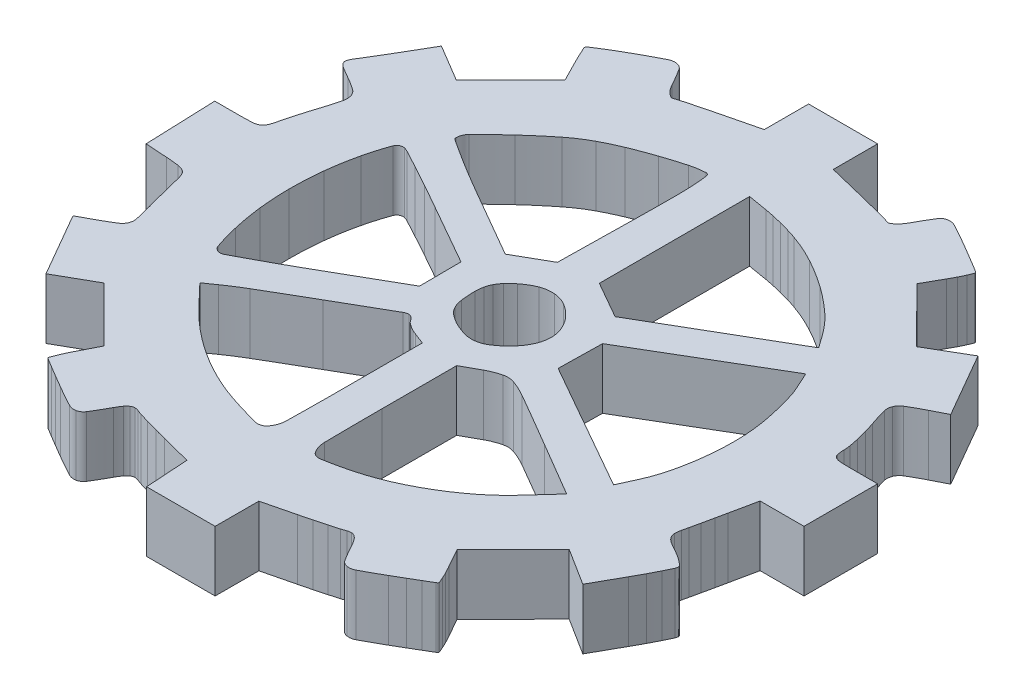
SolidWorks part; units mm, degrees
ref_plane "Front Plane" through (0, 0, 0) normal (0, 0, 1) x (1, 0, 0)
ref_plane "Top Plane" through (0, 0, 0) normal (0, 1, 0) x (1, 0, 0)
ref_plane "Right Plane" through (0, 0, 0) normal (1, 0, 0) x (0, 0, -1)
sketch "Sketch1" plane through (0, 0, 0) normal (0, 1, 0) x (1, 0, 0)
  line L30 (6921.7474, 9184.2888) -> (6921.7474, 9183.9218)
  line L31 (6921.7474, 9183.9218) -> (6921.195, 9183.7863)
  line L32 (6919.2339, 9183.2823) -> (6919.3873, 9182.9815)
  line L33 (6919.3873, 9182.9815) -> (6918.9372, 9182.5315)
  line L34 (6918.9372, 9182.5315) -> (6918.4872, 9182.0815)
  line L35 (6918.4872, 9182.0815) -> (6918.1815, 9182.2638)
  line L36 (6918.1815, 9182.2638) -> (6917.8757, 9182.4461)
  line L37 (6917.8757, 9182.4461) -> (6917.6654, 9182.0841)
  line L38 (6917.1708, 9179.7791) -> (6916.788, 9179.7791)
  line L39 (6916.788, 9179.7791) -> (6916.8103, 9179.1885)
  line L40 (6916.8103, 9179.1885) -> (6916.8325, 9178.598)
  line L41 (6916.8325, 9178.598) -> (6917.1941, 9178.5748)
  line L42 (6917.465, 9177.0712) -> (6917.2593, 9176.9598)
  line L43 (6917.2593, 9176.9598) -> (6917.5633, 9176.4325)
  line L44 (6917.5633, 9176.4325) -> (6917.8673, 9175.9052)
  line L45 (6917.8673, 9175.9052) -> (6918.1735, 9176.0791)
  line L46 (6918.1735, 9176.0791) -> (6918.4796, 9176.253)
  line L47 (6918.4796, 9176.253) -> (6918.9314, 9175.8012)
  line L48 (6918.9314, 9175.8012) -> (6919.3832, 9175.3494)
  line L49 (6919.3832, 9175.3494) -> (6919.2265, 9175.0423)
  line L50 (6921.214, 9174.5238) -> (6921.7093, 9174.3973)
  line L51 (6921.7093, 9174.3973) -> (6921.7326, 9174.0402)
  line L52 (6921.7326, 9174.0402) -> (6921.7558, 9173.6831)
  line L53 (6921.7558, 9173.6831) -> (6922.3231, 9173.6831)
  line L54 (6922.3231, 9173.6831) -> (6922.8904, 9173.6831)
  line L55 (6922.8904, 9173.6831) -> (6922.891, 9174.045)
  line L56 (6922.891, 9174.045) -> (6922.8915, 9174.407)
  line L57 (6922.8915, 9174.407) -> (6923.4053, 9174.533)
  line L58 (6925.3838, 9174.6199) -> (6925.5248, 9174.7034)
  line L59 (6925.4013, 9175.0451) -> (6925.2297, 9175.3504)
  line L60 (6925.2297, 9175.3504) -> (6925.692, 9175.8171)
  line L61 (6925.692, 9175.8171) -> (6926.1544, 9176.2838)
  line L62 (6926.1544, 9176.2838) -> (6926.4603, 9176.0907)
  line L63 (6926.4603, 9176.0907) -> (6926.7662, 9175.8976)
  line L64 (6926.7662, 9175.8976) -> (6927.0381, 9176.3839)
  line L65 (6926.9482, 9178.1217) -> (6927.0401, 9178.5599)
  line L66 (6927.0401, 9178.5599) -> (6927.4037, 9178.5599)
  line L67 (6927.4037, 9178.5599) -> (6927.7672, 9178.5599)
  line L68 (6927.7672, 9178.5599) -> (6927.7672, 9179.1695)
  line L69 (6927.7672, 9179.1695) -> (6927.7672, 9179.7791)
  line L70 (6927.7672, 9179.7791) -> (6927.3862, 9179.7791)
  line L71 (6927.1347, 9181.2554) -> (6927.3786, 9181.3792)
  line L72 (6927.3786, 9181.3792) -> (6927.0713, 9181.9122)
  line L73 (6927.0713, 9181.9122) -> (6926.764, 9182.4451)
  line L74 (6926.764, 9182.4451) -> (6926.4425, 9182.2567)
  line L75 (6926.4425, 9182.2567) -> (6926.121, 9182.0683)
  line L76 (6926.121, 9182.0683) -> (6925.6718, 9182.5222)
  line L77 (6925.6718, 9182.5222) -> (6925.2227, 9182.9761)
  line L78 (6925.2227, 9182.9761) -> (6925.3977, 9183.2876)
  line L79 (6923.4429, 9183.7863) -> (6922.8904, 9183.9218)
  line L80 (6922.8904, 9183.9218) -> (6922.8904, 9184.2888)
  line L81 (6922.8904, 9184.2888) -> (6922.8904, 9184.6559)
  line L82 (6922.8904, 9184.6559) -> (6922.3189, 9184.6559)
  line L83 (6922.3189, 9184.6559) -> (6921.7474, 9184.6559)
  line L84 (6921.7474, 9184.6559) -> (6921.7474, 9184.2888)
  line L85 (6921.9588, 9181.5656) -> (6921.9379, 9180.3042)
  line L86 (6921.9379, 9180.3042) -> (6921.6633, 9180.1473)
  line L87 (6921.6633, 9180.1473) -> (6921.3887, 9179.9905)
  line L88 (6921.3887, 9179.9905) -> (6920.3503, 9180.5896)
  line L89 (6925.1773, 9181.4542) -> (6925.3283, 9181.2422)
  line L90 (6925.3283, 9181.2422) -> (6924.2619, 9180.6226)
  line L91 (6924.2619, 9180.6226) -> (6923.1955, 9180.003)
  line L92 (6923.1955, 9180.003) -> (6922.8912, 9180.1768)
  line L93 (6922.8912, 9180.1768) -> (6922.5868, 9180.3506)
  line L94 (6922.5868, 9180.3506) -> (6922.5862, 9181.5955)
  line L95 (6922.5862, 9181.5955) -> (6922.5856, 9182.8405)
  line L96 (6922.5856, 9182.8405) -> (6922.9085, 9182.7859)
  line L97 (6925.7249, 9177.8626) -> (6925.5955, 9177.5778)
  line L98 (6925.5955, 9177.5778) -> (6924.5306, 9178.1835)
  line L99 (6924.5306, 9178.1835) -> (6923.4656, 9178.7892)
  line L100 (6923.4656, 9178.7892) -> (6923.4721, 9179.1508)
  line L101 (6923.4721, 9179.1508) -> (6923.4785, 9179.5124)
  line L102 (6923.4785, 9179.5124) -> (6924.537, 9180.1365)
  line L103 (6924.537, 9180.1365) -> (6925.5955, 9180.7606)
  line L104 (6925.5955, 9180.7606) -> (6925.7249, 9180.4761)
  line L105 (6920.1298, 9180.0839) -> (6921.1334, 9179.5124)
  line L106 (6921.1334, 9179.5124) -> (6921.1356, 9179.1667)
  line L107 (6921.1356, 9179.1667) -> (6921.1378, 9178.821)
  line L108 (6921.1378, 9178.821) -> (6920.1108, 9178.2333)
  line L109 (6921.7929, 9178.0999) -> (6921.976, 9178.0303)
  line L110 (6921.976, 9178.0303) -> (6921.976, 9176.7711)
  line L111 (6919.6138, 9176.691) -> (6919.2709, 9177.05)
  line L112 (6919.2709, 9177.05) -> (6919.452, 9177.1763)
  line L113 (6924.4381, 9177.5879) -> (6925.338, 9177.0582)
  line L114 (6925.338, 9177.0582) -> (6924.9564, 9176.6407)
  line L115 (6922.5858, 9176.7501) -> (6922.5861, 9177.9884)
  line L116 (6922.5861, 9177.9884) -> (6922.8716, 9178.1465)
  arc A414 (6921.195, 9183.7863) -> (6920.9768, 9183.7318) centre (6927.4959, 9158.0872) ccw
  arc A415 (6920.9768, 9183.7318) -> (6920.7782, 9183.6802) centre (6925.4996, 9165.9402) ccw
  arc A416 (6920.7782, 9183.6802) -> (6920.6122, 9183.6353) centre (6926.2112, 9163.2663) ccw
  arc A417 (6920.6122, 9183.6353) -> (6920.5518, 9183.6151) centre (6920.7702, 9183.0603) ccw
  arc A418 (6920.5087, 9183.6167) -> (6920.5518, 9183.6151) centre (6920.532, 9183.6652) ccw
  arc A419 (6920.4536, 9183.6529) -> (6920.5087, 9183.6167) centre (6920.6174, 9183.8424) ccw
  arc A420 (6920.3961, 9183.7143) -> (6920.4536, 9183.6529) centre (6920.7139, 9183.9542) ccw
  arc A421 (6920.345, 9183.7938) -> (6920.3961, 9183.7143) centre (6920.8975, 9184.0926) ccw
  arc A422 (6920.345, 9183.7938) -> (6920.1788, 9184.0777) centre (6916.0619, 9181.4769) ccw
  arc A423 (6920.1788, 9184.0777) -> (6920.0775, 9184.1463) centre (6920.0498, 9183.9962) ccw
  arc A424 (6920.0775, 9184.1463) -> (6919.9461, 9184.1272) centre (6920.0399, 9183.9429) ccw
  arc A425 (6919.9461, 9184.1272) -> (6919.5848, 9183.9343) centre (6924.7426, 9174.7113) ccw
  arc A426 (6919.5848, 9183.9343) -> (6919.3915, 9183.8236) centre (6925.1484, 9173.9858) ccw
  arc A427 (6919.3915, 9183.8236) -> (6919.2286, 9183.7249) centre (6922.4798, 9178.5461) ccw
  arc A428 (6919.2286, 9183.7249) -> (6919.0914, 9183.6377) centre (6927.0862, 9171.2084) ccw
  arc A429 (6919.0914, 9183.6377) -> (6919.0804, 9183.6176) centre (6919.1043, 9183.6176) ccw
  arc A430 (6919.0804, 9183.6176) -> (6919.0854, 9183.5941) centre (6919.1387, 9183.6176) ccw
  arc A431 (6919.0854, 9183.5941) -> (6919.1255, 9183.5048) centre (6925.7773, 9186.5484) ccw
  arc A432 (6919.1255, 9183.5048) -> (6919.1751, 9183.4) centre (6923.2943, 9185.4123) ccw
  arc A433 (6919.1751, 9183.4) -> (6919.2339, 9183.2823) centre (6925.9976, 9186.7329) ccw
  arc A434 (6917.5771, 9181.9335) -> (6917.6654, 9182.0841) centre (6897.4845, 9193.8123) ccw
  arc A435 (6917.4857, 9181.7803) -> (6917.5771, 9181.9335) centre (6895.6617, 9194.89) ccw
  arc A436 (6917.4038, 9181.6448) -> (6917.4857, 9181.7803) centre (6898.0197, 9193.4735) ccw
  arc A437 (6917.3493, 9181.5579) -> (6917.4038, 9181.6448) centre (6913.7664, 9183.8644) ccw
  arc A438 (6917.3493, 9181.5579) -> (6917.2992, 9181.4576) centre (6917.7826, 9181.279) ccw
  arc A439 (6917.2992, 9181.4576) -> (6917.3053, 9181.3922) centre (6917.3704, 9181.4313) ccw
  arc A440 (6917.3053, 9181.3922) -> (6917.3666, 9181.33) centre (6917.4653, 9181.4884) ccw
  arc A441 (6917.3666, 9181.33) -> (6917.5524, 9181.22) centre (6919.9107, 9185.4161) ccw
  arc A442 (6917.7657, 9181.0847) -> (6917.5524, 9181.22) centre (6916.3889, 9179.1498) ccw
  arc A443 (6917.8392, 9180.9816) -> (6917.7657, 9181.0847) centre (6917.6534, 9180.927) ccw
  arc A444 (6917.8416, 9180.843) -> (6917.8392, 9180.9816) centre (6917.588, 9180.9078) ccw
  arc A445 (6917.7533, 9180.5356) -> (6917.8416, 9180.843) centre (6912.6422, 9182.1707) ccw
  arc A446 (6917.7533, 9180.5356) -> (6917.7086, 9180.3911) centre (6925.1508, 9178.169) ccw
  arc A447 (6917.7086, 9180.3911) -> (6917.6636, 9180.2358) centre (6927.4202, 9177.4914) ccw
  arc A448 (6917.6636, 9180.2358) -> (6917.6245, 9180.0923) centre (6926.545, 9177.7376) ccw
  arc A449 (6917.6245, 9180.0923) -> (6917.5994, 9179.9886) centre (6920.0543, 9179.4509) ccw
  arc A450 (6917.5597, 9179.8696) -> (6917.5994, 9179.9886) centre (6917.0231, 9180.1149) ccw
  arc A451 (6917.5025, 9179.8109) -> (6917.5597, 9179.8696) centre (6917.4491, 9179.9201) ccw
  arc A452 (6917.4013, 9179.7848) -> (6917.5025, 9179.8109) centre (6917.3884, 9180.0441) ccw
  arc A453 (6917.1708, 9179.7791) -> (6917.4013, 9179.7848) centre (6917.1708, 9184.4409) ccw
  arc A454 (6917.4021, 9178.5549) -> (6917.1941, 9178.5748) centre (6916.9789, 9175.2233) ccw
  arc A455 (6917.5033, 9178.5215) -> (6917.4021, 9178.5549) centre (6917.367, 9178.279) ccw
  arc A456 (6917.5616, 9178.4595) -> (6917.5033, 9178.5215) centre (6917.4338, 9178.3978) ccw
  arc A457 (6917.6008, 9178.3462) -> (6917.5616, 9178.4595) centre (6917.0983, 9178.2357) ccw
  arc A458 (6917.6008, 9178.3462) -> (6917.6256, 9178.2399) centre (6921.6161, 9179.229) ccw
  arc A459 (6917.6256, 9178.2399) -> (6917.6659, 9178.0803) centre (6937.2079, 9183.0936) ccw
  arc A460 (6917.6659, 9178.0803) -> (6917.7124, 9177.902) centre (6939.5362, 9183.691) ccw
  arc A461 (6917.7124, 9177.902) -> (6917.759, 9177.7295) centre (6937.0246, 9183.0248) ccw
  arc A462 (6917.8299, 9177.4382) -> (6917.759, 9177.7295) centre (6912.8294, 9176.3746) ccw
  arc A463 (6917.8174, 9177.3193) -> (6917.8299, 9177.4382) centre (6917.6411, 9177.398) ccw
  arc A464 (6917.7372, 9177.2281) -> (6917.8174, 9177.3193) centre (6917.6303, 9177.4028) ccw
  arc A465 (6917.465, 9177.0712) -> (6917.7372, 9177.2281) centre (6914.5971, 9182.3632) ccw
  arc A466 (6919.2265, 9175.0423) -> (6919.1682, 9174.9229) centre (6922.6182, 9173.312) ccw
  arc A467 (6919.1682, 9174.9229) -> (6919.123, 9174.8186) centre (6921.0217, 9174.0574) ccw
  arc A468 (6919.123, 9174.8186) -> (6919.0896, 9174.7315) centre (6921.9291, 9173.6936) ccw
  arc A469 (6919.0896, 9174.7315) -> (6919.0942, 9174.7122) centre (6919.1065, 9174.7253) ccw
  arc A470 (6919.0942, 9174.7122) -> (6919.1142, 9174.697) centre (6919.1761, 9174.7993) ccw
  arc A471 (6919.1142, 9174.697) -> (6919.2539, 9174.6128) centre (6951.9822, 9229.0583) ccw
  arc A472 (6919.2539, 9174.6128) -> (6919.4161, 9174.5161) centre (6932.0019, 9195.8198) ccw
  arc A473 (6919.4161, 9174.5161) -> (6919.6038, 9174.4059) centre (6941.6383, 9212.1311) ccw
  arc A474 (6919.6038, 9174.4059) -> (6919.9513, 9174.2122) centre (6924.5615, 9182.894) ccw
  arc A475 (6919.9513, 9174.2122) -> (6920.0793, 9174.1928) centre (6920.0429, 9174.3848) ccw
  arc A476 (6920.0793, 9174.1928) -> (6920.179, 9174.2608) centre (6920.0512, 9174.341) ccw
  arc A477 (6920.179, 9174.2608) -> (6920.3457, 9174.5465) centre (6915.8487, 9176.9784) ccw
  arc A478 (6920.4077, 9174.646) -> (6920.3457, 9174.5465) centre (6921.1829, 9174.0938) ccw
  arc A479 (6920.4649, 9174.701) -> (6920.4077, 9174.646) centre (6920.5817, 9174.522) ccw
  arc A480 (6920.5242, 9174.7194) -> (6920.4649, 9174.701) centre (6920.5269, 9174.6061) ccw
  arc A481 (6920.5905, 9174.7063) -> (6920.5242, 9174.7194) centre (6920.5279, 9174.5627) ccw
  arc A482 (6920.5905, 9174.7063) -> (6920.668, 9174.6775) centre (6920.8911, 9175.3956) ccw
  arc A483 (6920.668, 9174.6775) -> (6920.8266, 9174.6297) centre (6923.6345, 9184.2232) ccw
  arc A484 (6920.8266, 9174.6297) -> (6921.015, 9174.5764) centre (6923.7909, 9184.7576) ccw
  arc A485 (6921.015, 9174.5764) -> (6921.214, 9174.5238) centre (6924.4053, 9187.0112) ccw
  arc A486 (6923.4053, 9174.533) -> (6923.6114, 9174.5851) centre (6919.6517, 9189.8362) ccw
  arc A487 (6923.6114, 9174.5851) -> (6923.8059, 9174.6372) centre (6920.4284, 9186.8446) ccw
  arc A488 (6923.8059, 9174.6372) -> (6923.9693, 9174.6837) centre (6920.5606, 9186.3669) ccw
  arc A489 (6923.9693, 9174.6837) -> (6924.0473, 9174.7107) centre (6923.7351, 9175.4865) ccw
  arc A490 (6924.113, 9174.721) -> (6924.0473, 9174.7107) centre (6924.1025, 9174.5736) ccw
  arc A491 (6924.1729, 9174.7004) -> (6924.113, 9174.721) centre (6924.1042, 9174.598) ccw
  arc A492 (6924.2309, 9174.6443) -> (6924.1729, 9174.7004) centre (6924.0459, 9174.511) ccw
  arc A493 (6924.2922, 9174.5465) -> (6924.2309, 9174.6443) centre (6923.5016, 9174.119) ccw
  arc A494 (6924.2922, 9174.5465) -> (6924.4549, 9174.2689) centre (6928.4083, 9176.7725) ccw
  arc A495 (6924.4549, 9174.2689) -> (6924.5547, 9174.2018) centre (6924.5811, 9174.3488) ccw
  arc A496 (6924.5547, 9174.2018) -> (6924.6836, 9174.2218) centre (6924.5901, 9174.3992) ccw
  arc A497 (6924.6836, 9174.2218) -> (6925.0313, 9174.4139) centre (6920.0885, 9182.9491) ccw
  arc A498 (6925.0313, 9174.4139) -> (6925.2203, 9174.5238) centre (6894.1557, 9227.7293) ccw
  arc A499 (6925.2203, 9174.5238) -> (6925.3838, 9174.6199) centre (6907.548, 9204.7917) ccw
  arc A500 (6925.5248, 9174.7034) -> (6925.5461, 9174.7182) centre (6925.4337, 9174.8568) ccw
  arc A501 (6925.5461, 9174.7182) -> (6925.551, 9174.7371) centre (6925.5357, 9174.731) ccw
  arc A502 (6925.551, 9174.7371) -> (6925.5146, 9174.8232) centre (6922.9721, 9173.6969) ccw
  arc A503 (6925.5146, 9174.8232) -> (6925.4651, 9174.9266) centre (6923.7296, 9174.0325) ccw
  arc A504 (6925.4651, 9174.9266) -> (6925.4013, 9175.0451) centre (6922.1686, 9173.2283) ccw
  arc A505 (6927.0381, 9176.3839) -> (6927.1423, 9176.575) centre (6918.1453, 9181.357) ccw
  arc A506 (6927.1423, 9176.575) -> (6927.2302, 9176.7466) centre (6921.5898, 9179.5262) ccw
  arc A507 (6927.2302, 9176.7466) -> (6927.3003, 9176.8922) centre (6919.1656, 9180.7209) ccw
  arc A508 (6927.3003, 9176.8922) -> (6927.31, 9176.9357) centre (6927.208, 9176.9357) ccw
  arc A509 (6927.31, 9176.9357) -> (6927.2955, 9176.9691) centre (6927.2643, 9176.9357) ccw
  arc A510 (6927.2955, 9176.9691) -> (6927.2299, 9177.0251) centre (6926.6393, 9176.2669) ccw
  arc A511 (6927.2299, 9177.0251) -> (6927.1418, 9177.0871) centre (6926.5559, 9176.1597) ccw
  arc A512 (6927.1418, 9177.0871) -> (6927.0374, 9177.1481) centre (6926.212, 9175.6154) ccw
  arc A513 (6926.8914, 9177.235) -> (6927.0374, 9177.1481) centre (6927.9719, 9178.8833) ccw
  arc A514 (6926.8224, 9177.3035) -> (6926.8914, 9177.235) centre (6927.0242, 9177.4377) ccw
  arc A515 (6926.7986, 9177.3806) -> (6926.8224, 9177.3035) centre (6926.9411, 9177.3825) ccw
  arc A516 (6926.8105, 9177.4893) -> (6926.7986, 9177.3806) centre (6927.2469, 9177.3864) ccw
  arc A517 (6926.8105, 9177.4893) -> (6926.8341, 9177.5925) centre (6919.1051, 9179.3051) ccw
  arc A518 (6926.8341, 9177.5925) -> (6926.8698, 9177.7552) centre (6882.6805, 9187.3764) ccw
  arc A519 (6926.8698, 9177.7552) -> (6926.9097, 9177.9397) centre (6877.2854, 9188.5511) ccw
  arc A520 (6926.9097, 9177.9397) -> (6926.9482, 9178.1217) centre (6880.1182, 9187.9454) ccw
  arc A521 (6927.1485, 9179.7839) -> (6927.3862, 9179.7791) centre (6927.3862, 9185.6677) ccw
  arc A522 (6927.0588, 9179.8087) -> (6927.1485, 9179.7839) centre (6927.1568, 9179.988) ccw
  arc A523 (6927.0164, 9179.8657) -> (6927.0588, 9179.8087) centre (6927.0996, 9179.8834) ccw
  arc A524 (6927.0028, 9179.9886) -> (6927.0164, 9179.8657) centre (6927.6302, 9179.9961) ccw
  arc A525 (6927.0028, 9179.9886) -> (6926.9927, 9180.0959) centre (6926.3441, 9179.9808) ccw
  arc A526 (6926.9927, 9180.0959) -> (6926.9604, 9180.2542) centre (6923.8889, 9179.5452) ccw
  arc A527 (6926.9604, 9180.2542) -> (6926.9151, 9180.4299) centre (6923.4843, 9179.4518) ccw
  arc A528 (6926.9151, 9180.4299) -> (6926.862, 9180.5985) centre (6923.8174, 9179.5468) ccw
  arc A529 (6926.776, 9180.8814) -> (6926.862, 9180.5985) centre (6930.5881, 9181.8858) ccw
  arc A530 (6926.7848, 9181.0103) -> (6926.776, 9180.8814) centre (6926.9713, 9180.9328) ccw
  arc A531 (6926.8699, 9181.109) -> (6926.7848, 9181.0103) centre (6926.9771, 9180.9304) ccw
  arc A532 (6927.1347, 9181.2554) -> (6926.8699, 9181.109) centre (6929.0714, 9177.4413) ccw
  arc A533 (6925.3977, 9183.2876) -> (6925.4629, 9183.4088) centre (6922.1922, 9185.0892) ccw
  arc A534 (6925.4629, 9183.4088) -> (6925.5135, 9183.515) centre (6923.7109, 9184.309) ccw
  arc A535 (6925.5135, 9183.515) -> (6925.5507, 9183.6035) centre (6923.0126, 9184.6165) ccw
  arc A536 (6925.5507, 9183.6035) -> (6925.5461, 9183.6244) centre (6925.533, 9183.6106) ccw
  arc A537 (6925.5461, 9183.6244) -> (6925.5242, 9183.6411) centre (6925.4569, 9183.5301) ccw
  arc A538 (6925.5242, 9183.6411) -> (6925.3846, 9183.7255) centre (6897.9936, 9138.2987) ccw
  arc A539 (6925.3846, 9183.7255) -> (6925.222, 9183.8227) centre (6913.7705, 9164.464) ccw
  arc A540 (6925.222, 9183.8227) -> (6925.0341, 9183.9331) centre (6905.2189, 9150.0076) ccw
  arc A541 (6925.0341, 9183.9331) -> (6924.6867, 9184.1267) centre (6920.0712, 9175.4362) ccw
  arc A542 (6924.6867, 9184.1267) -> (6924.5587, 9184.1462) centre (6924.5949, 9183.9538) ccw
  arc A543 (6924.5587, 9184.1462) -> (6924.459, 9184.0784) centre (6924.5865, 9183.9983) ccw
  arc A544 (6924.459, 9184.0784) -> (6924.2929, 9183.7938) centre (6928.7432, 9181.3865) ccw
  arc A545 (6924.2418, 9183.7143) -> (6924.2929, 9183.7938) centre (6923.7404, 9184.0926) ccw
  arc A546 (6924.1843, 9183.6529) -> (6924.2418, 9183.7143) centre (6923.9239, 9183.9542) ccw
  arc A547 (6924.1292, 9183.6167) -> (6924.1843, 9183.6529) centre (6924.0205, 9183.8424) ccw
  arc A548 (6924.0861, 9183.6151) -> (6924.1292, 9183.6167) centre (6924.1059, 9183.6652) ccw
  arc A549 (6924.0861, 9183.6151) -> (6924.0257, 9183.6353) centre (6923.8677, 9183.0603) ccw
  arc A550 (6924.0257, 9183.6353) -> (6923.8597, 9183.6802) centre (6918.4267, 9163.2663) ccw
  arc A551 (6923.8597, 9183.6802) -> (6923.6611, 9183.7318) centre (6919.1383, 9165.9402) ccw
  arc A552 (6923.6611, 9183.7318) -> (6923.4429, 9183.7863) centre (6917.142, 9158.0872) ccw
  arc A553 (6919.9521, 9180.8238) -> (6920.3503, 9180.5896) centre (6934.3687, 9204.8853) ccw
  arc A554 (6919.6165, 9181.0309) -> (6919.9521, 9180.8238) centre (6927.6447, 9193.6629) ccw
  arc A555 (6919.3308, 9181.2141) -> (6919.6165, 9181.0309) centre (6942.1356, 9216.4633) ccw
  arc A556 (6919.3105, 9181.2505) -> (6919.3308, 9181.2141) centre (6919.355, 9181.2515) ccw
  arc A557 (6919.3732, 9181.4075) -> (6919.3105, 9181.2505) centre (6919.5258, 9181.2555) ccw
  arc A558 (6919.7627, 9181.7811) -> (6919.3732, 9181.4075) centre (6927.8224, 9172.9902) ccw
  arc A559 (6920.1817, 9182.1381) -> (6919.7627, 9181.7811) centre (6924.8604, 9176.221) ccw
  arc A560 (6920.5198, 9182.3592) -> (6920.1817, 9182.1381) centre (6921.5807, 9180.3687) ccw
  arc A561 (6920.8503, 9182.5148) -> (6920.5198, 9182.3592) centre (6922.245, 9179.1225) ccw
  arc A562 (6921.25, 9182.6647) -> (6920.8503, 9182.5148) centre (6923.4404, 9176.2147) ccw
  arc A563 (6921.6318, 9182.7817) -> (6921.25, 9182.6647) centre (6923.3966, 9176.3438) ccw
  arc A564 (6921.8826, 9182.8221) -> (6921.6318, 9182.7817) centre (6921.9434, 9181.645) ccw
  arc A565 (6921.9326, 9182.7812) -> (6921.8826, 9182.8221) centre (6921.8851, 9182.7741) ccw
  arc A566 (6921.9552, 9182.5644) -> (6921.9326, 9182.7812) centre (6919.4488, 9182.4124) ccw
  arc A567 (6921.9654, 9182.2071) -> (6921.9552, 9182.5644) centre (6916.4172, 9182.2285) ccw
  arc A568 (6921.9588, 9181.5656) -> (6921.9654, 9182.2071) centre (6871.4558, 9182.4021) ccw
  arc A569 (6923.9988, 9182.4184) -> (6923.5346, 9182.6244) centre (6922.4582, 9179.5735) ccw
  arc A570 (6924.467, 9182.1264) -> (6923.9988, 9182.4184) centre (6921.8549, 9178.4595) ccw
  arc A571 (6924.8805, 9181.7908) -> (6924.467, 9182.1264) centre (6922.0002, 9178.6633) ccw
  arc A572 (6925.1773, 9181.4542) -> (6924.8805, 9181.7908) centre (6923.4144, 9180.1989) ccw
  arc A573 (6923.0541, 9182.7573) -> (6922.9085, 9182.7859) centre (6922.4445, 9180.0397) ccw
  arc A574 (6923.2256, 9182.716) -> (6923.0541, 9182.7573) centre (6921.842, 9177.3537) ccw
  arc A575 (6923.3952, 9182.6693) -> (6923.2256, 9182.716) centre (6921.8474, 9177.3745) ccw
  arc A576 (6923.5346, 9182.6244) -> (6923.3952, 9182.6693) centre (6922.6447, 9180.102) ccw
  arc A577 (6925.9732, 9179.2256) -> (6925.9359, 9179.6805) centre (6922.9956, 9179.2108) ccw
  arc A578 (6925.9458, 9178.7315) -> (6925.9732, 9179.2256) centre (6921.8647, 9179.2052) ccw
  arc A579 (6925.861, 9178.257) -> (6925.9458, 9178.7315) centre (6922.0403, 9179.1848) ccw
  arc A580 (6925.7249, 9177.8626) -> (6925.861, 9178.257) centre (6923.7027, 9178.7811) ccw
  arc A581 (6925.7803, 9180.3317) -> (6925.7249, 9180.4761) centre (6924.562, 9179.9473) ccw
  arc A582 (6925.8403, 9180.125) -> (6925.7803, 9180.3317) centre (6921.3545, 9178.9352) ccw
  arc A583 (6925.8952, 9179.897) -> (6925.8403, 9180.125) centre (6920.8828, 9178.8101) ccw
  arc A584 (6925.9359, 9179.6805) -> (6925.8952, 9179.897) centre (6921.9892, 9179.05) ccw
  arc A585 (6919.7119, 9178.008) -> (6920.1108, 9178.2333) centre (6899.8769, 9213.591) ccw
  arc A586 (6919.3643, 9177.8181) -> (6919.7119, 9178.008) centre (6908.5907, 9197.9589) ccw
  arc A587 (6919.063, 9177.6581) -> (6919.3643, 9177.8181) centre (6892.4533, 9228.1269) ccw
  arc A588 (6919.012, 9177.6455) -> (6919.063, 9177.6581) centre (6919.012, 9177.7549) ccw
  arc A589 (6918.8945, 9177.7299) -> (6919.012, 9177.6455) centre (6919.012, 9177.7695) ccw
  arc A590 (6918.78, 9178.132) -> (6918.8945, 9177.7299) centre (6923.043, 9179.1282) ccw
  arc A591 (6918.6945, 9178.6252) -> (6918.78, 9178.132) centre (6923.0035, 9179.119) ccw
  arc A592 (6918.6648, 9179.1314) -> (6918.6945, 9178.6252) centre (6923.2349, 9179.1455) ccw
  arc A593 (6918.6936, 9179.6806) -> (6918.6648, 9179.1314) centre (6923.6183, 9179.1467) ccw
  arc A594 (6918.7833, 9180.2027) -> (6918.6936, 9179.6806) centre (6922.9378, 9179.2204) ccw
  arc A595 (6918.9048, 9180.6121) -> (6918.7833, 9180.2027) centre (6922.4736, 9179.3302) ccw
  arc A596 (6919.0307, 9180.6794) -> (6918.9048, 9180.6121) centre (6919.0049, 9180.5762) ccw
  arc A597 (6919.0973, 9180.6537) -> (6919.0307, 9180.6794) centre (6918.9599, 9180.3965) ccw
  arc A598 (6919.393, 9180.4946) -> (6919.0973, 9180.6537) centre (6891.5804, 9129.157) ccw
  arc A599 (6919.7384, 9180.3046) -> (6919.393, 9180.4946) centre (6904.5446, 9153.0867) ccw
  arc A600 (6920.1298, 9180.0839) -> (6919.7384, 9180.3046) centre (6894.112, 9134.3982) ccw
  arc A601 (6922.9263, 9179.3712) -> (6922.7952, 9179.5844) centre (6922.241, 9179.0967) ccw
  arc A602 (6922.9631, 9179.1451) -> (6922.9263, 9179.3712) centre (6922.4383, 9179.1757) ccw
  arc A603 (6922.9003, 9178.9191) -> (6922.9631, 9179.1451) centre (6922.4078, 9179.1775) ccw
  arc A604 (6922.7439, 9178.7064) -> (6922.9003, 9178.9191) centre (6922.1237, 9179.3266) ccw
  arc A605 (6922.5622, 9178.5602) -> (6922.7439, 9178.7064) centre (6921.9772, 9179.4732) ccw
  arc A606 (6922.3895, 9178.4957) -> (6922.5622, 9178.5602) centre (6922.3264, 9178.9281) ccw
  arc A607 (6922.2037, 9178.5076) -> (6922.3895, 9178.4957) centre (6922.3247, 9178.9396) ccw
  arc A608 (6921.9815, 9178.5952) -> (6922.2037, 9178.5076) centre (6922.52, 9179.6366) ccw
  arc A609 (6921.827, 9178.6977) -> (6921.9815, 9178.5952) centre (6922.3744, 9179.355) ccw
  arc A610 (6921.734, 9178.8144) -> (6921.827, 9178.6977) centre (6922.0632, 9178.9814) ccw
  arc A611 (6921.6858, 9178.9719) -> (6921.734, 9178.8144) centre (6922.1614, 9179.0312) ccw
  arc A612 (6921.6712, 9179.2071) -> (6921.6858, 9178.9719) centre (6923.5733, 9179.2071) ccw
  arc A613 (6921.6844, 9179.3396) -> (6921.6712, 9179.2071) centre (6922.3439, 9179.2071) ccw
  arc A614 (6921.7238, 9179.45) -> (6921.6844, 9179.3396) centre (6922.0837, 9179.2593) ccw
  arc A615 (6921.7969, 9179.5532) -> (6921.7238, 9179.45) centre (6922.1581, 9179.2199) ccw
  arc A616 (6921.9137, 9179.6648) -> (6921.7969, 9179.5532) centre (6922.739, 9178.684) ccw
  arc A617 (6922.1373, 9179.7972) -> (6921.9137, 9179.6648) centre (6922.4233, 9179.0592) ccw
  arc A618 (6922.3663, 9179.8293) -> (6922.1373, 9179.7972) centre (6922.3204, 9179.3248) ccw
  arc A619 (6922.5893, 9179.7563) -> (6922.3663, 9179.8293) centre (6922.3187, 9179.3069) ccw
  arc A620 (6922.7952, 9179.5844) -> (6922.5893, 9179.7563) centre (6922.1371, 9179.0053) ccw
  arc A621 (6921.5598, 9178.2504) -> (6921.5914, 9178.2146) centre (6921.6813, 9178.3255) ccw
  arc A622 (6921.5914, 9178.2146) -> (6921.6489, 9178.1728) centre (6922.0061, 9178.7259) ccw
  arc A623 (6921.6489, 9178.1728) -> (6921.7192, 9178.1325) centre (6922.0703, 9178.8253) ccw
  arc A624 (6921.7192, 9178.1325) -> (6921.7929, 9178.0999) centre (6922.0642, 9178.8133) ccw
  arc A625 (6921.9677, 9175.7867) -> (6921.976, 9176.7711) centre (6863.599, 9176.7711) ccw
  arc A626 (6921.8978, 9175.5717) -> (6921.9677, 9175.7867) centre (6921.5827, 9175.7932) ccw
  arc A627 (6921.7337, 9175.5111) -> (6921.8978, 9175.5717) centre (6921.7718, 9175.6602) ccw
  arc A628 (6921.2012, 9175.6686) -> (6921.7337, 9175.5111) centre (6923.5755, 9182.7167) ccw
  arc A629 (6920.7715, 9175.8449) -> (6921.2012, 9175.6686) centre (6922.3544, 9179.0919) ccw
  arc A630 (6920.3556, 9176.0791) -> (6920.7715, 9175.8449) centre (6922.5366, 9179.4654) ccw
  arc A631 (6919.9657, 9176.3638) -> (6920.3556, 9176.0791) centre (6922.586, 9179.5422) ccw
  arc A632 (6919.6138, 9176.691) -> (6919.9657, 9176.3638) centre (6922.5365, 9179.4821) ccw
  arc A633 (6919.7701, 9177.3801) -> (6919.452, 9177.1763) centre (6922.1997, 9173.2368) ccw
  arc A634 (6920.5341, 9177.8238) -> (6919.7701, 9177.3801) centre (6973.8002, 9085.2427) ccw
  arc A635 (6921.3764, 9178.3074) -> (6920.5341, 9177.8238) centre (7176.0044, 8733.7952) ccw
  arc A636 (6921.4572, 9178.33) -> (6921.3764, 9178.3074) centre (6921.4615, 9178.1589) ccw
  arc A637 (6921.481, 9178.3247) -> (6921.4572, 9178.33) centre (6921.4585, 9178.2792) ccw
  arc A638 (6921.5091, 9178.3071) -> (6921.481, 9178.3247) centre (6921.4075, 9178.1762) ccw
  arc A639 (6921.5368, 9178.2813) -> (6921.5091, 9178.3071) centre (6921.3815, 9178.1427) ccw
  arc A640 (6921.5598, 9178.2504) -> (6921.5368, 9178.2813) centre (6921.3726, 9178.1347) ccw
  arc A641 (6924.6061, 9176.3155) -> (6924.9564, 9176.6407) centre (6922.8024, 9178.6093) ccw
  arc A642 (6924.1781, 9176.0212) -> (6924.6061, 9176.3155) centre (6922.0972, 9179.5062) ccw
  arc A643 (6923.711, 9175.781) -> (6924.1781, 9176.0212) centre (6922.0545, 9179.5777) ccw
  arc A644 (6923.2434, 9175.6178) -> (6923.711, 9175.781) centre (6922.3996, 9178.7869) ccw
  arc A645 (6922.7941, 9175.5201) -> (6923.2434, 9175.6178) centre (6921.9612, 9180.4333) ccw
  arc A646 (6922.65, 9175.5877) -> (6922.7941, 9175.5201) centre (6922.7707, 9175.6578) ccw
  arc A647 (6922.5924, 9175.796) -> (6922.65, 9175.5877) centre (6923.0188, 9175.8018) ccw
  arc A648 (6922.5858, 9176.7501) -> (6922.5924, 9175.796) centre (6990.8815, 9176.7388) ccw
  arc A649 (6923.1013, 9178.2364) -> (6922.8716, 9178.1465) centre (6923.323, 9177.3311) ccw
  arc A650 (6923.2875, 9178.2268) -> (6923.1013, 9178.2364) centre (6923.1785, 9177.9211) ccw
  arc A651 (6923.5535, 9178.1038) -> (6923.2875, 9178.2268) centre (6922.7444, 9176.7037) ccw
  arc A652 (6924.4381, 9177.5879) -> (6923.5535, 9178.1038) centre (6858.9544, 9066.3273) ccw
extrude "Boss-Extrude2" add sketch "Sketch1" along normal blind 1
scale "Scale1" bodies to scale 102 scale about centroid uniform scaling yes scale factor 25
